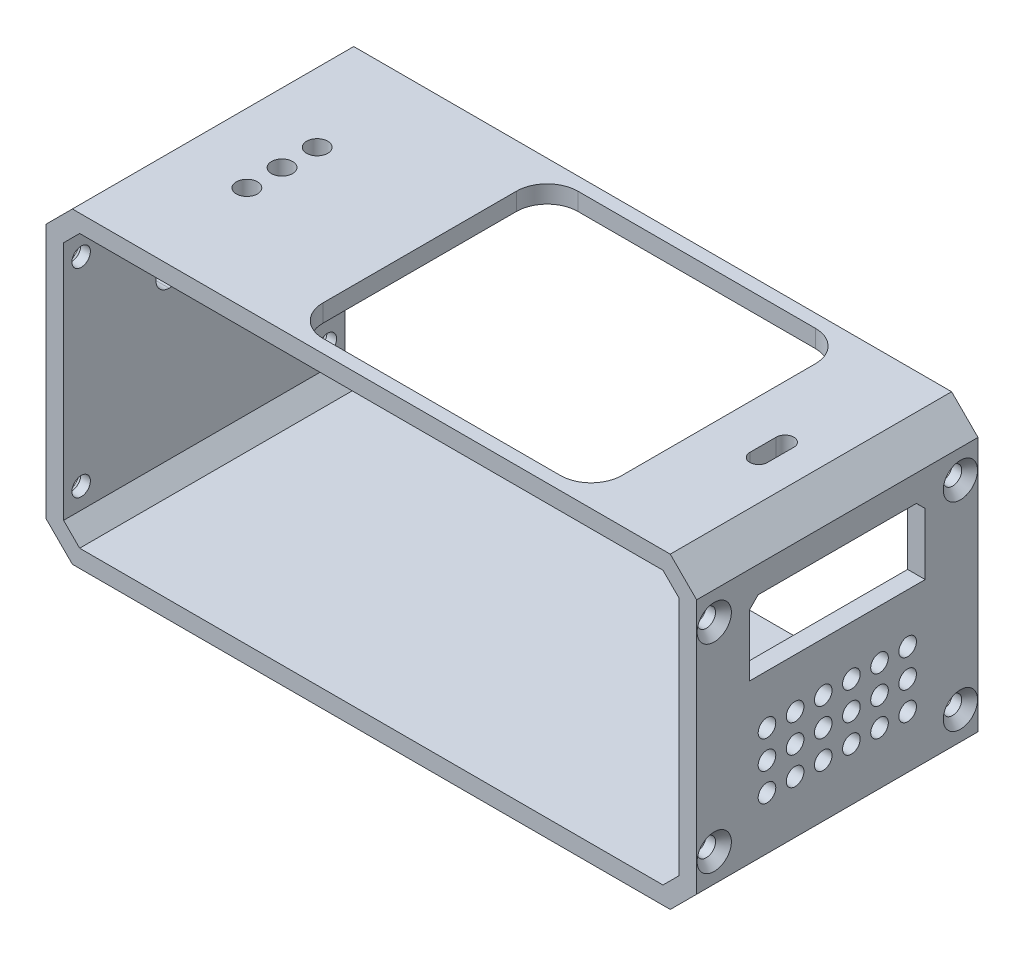
SolidWorks part; units mm, degrees
ref_plane "前视基准面" through (0, 0, 0) normal (0, 0, 1) x (1, 0, 0)
ref_plane "上视基准面" through (0, 0, 0) normal (0, 1, 0) x (1, 0, 0)
ref_plane "右视基准面" through (0, 0, 0) normal (1, 0, 0) x (0, 0, -1)
other "Configuration Table"
sketch "草图1" plane through (0, 0, 0) normal (0, 1, 0) x (1, 0, 0)
  line L0 (-32.2834, 0.435) -> (-71.9856, 0.435) construction
  line L1 (-36.9634, 16.435) -> (37.0366, 16.435)
  line L2 (-36.9634, 16.435) -> (-36.9634, -15.565)
  line L3 (-36.9634, -15.565) -> (37.0366, -15.565)
  line L4 (37.0366, 16.435) -> (37.0366, -15.565)
  line L6 (-32.2834, 11.935) -> (-32.2834, -11.065) construction
  point P6 (-36.9634, 0.435)
  point P9 (-32.2834, 0.435)
  dimension "D1" = 32
  dimension "D2" = 74
extrude "凸台-拉伸1" add sketch "草图1" along normal blind 35
chamfer "倒角1" distance 3 angle 45 4 edges at (37.0366, 0, -0.435) (-36.9634, 0, -0.435) (-36.9634, 35, -0.435) (37.0366, 35, -0.435)
sketch "草图2" plane through (0, 0, 15.565) normal (0, 0, 1) x (1, 0, 0)
  line L8 (-33.135, 2) -> (33.2082, 2)
  line L9 (35.0366, 3.8284) -> (35.0366, 31.1716)
  line L10 (33.2082, 33) -> (-33.135, 33)
  line L11 (-34.9634, 31.1716) -> (-34.9634, 3.8284)
  line L12 (-33.135, 2) -> (33.2082, 2)
  line L13 (35.0366, 3.8284) -> (35.0366, 31.1716)
  line L14 (33.2082, 33) -> (-33.135, 33)
  line L15 (-34.9634, 31.1716) -> (-34.9634, 3.8284)
  line L16 (33.2082, 2) -> (35.0366, 3.8284)
  line L17 (33.2082, 2) -> (35.0366, 3.8284)
  line L18 (35.0366, 31.1716) -> (33.2082, 33)
  line L19 (35.0366, 31.1716) -> (33.2082, 33)
  line L20 (-33.135, 33) -> (-34.9634, 31.1716)
  line L21 (-33.135, 33) -> (-34.9634, 31.1716)
  line L22 (-34.9634, 3.8284) -> (-33.135, 2)
  line L23 (-34.9634, 3.8284) -> (-33.135, 2)
  dimension "D1" = 2
extrude "切除-拉伸1" cut sketch "草图2" against normal through all
sketch "草图4" plane through (0, 35, 0) normal (0, 1, 0) x (1, 0, 0)
  line L0 (34.0366, 16.435) -> (-33.9634, 16.435) construction
  line L1 (-6.9634, 14.935) -> (20.0366, 14.935)
  line L2 (-10.4634, 11.435) -> (-10.4634, -10.565)
  line L3 (-6.9634, -14.065) -> (20.0366, -14.065)
  line L4 (23.5366, 11.435) -> (23.5366, -10.565)
  line L5 (-33.9634, -15.565) -> (34.0366, -15.565) construction
  line L7 (37.0366, 16.435) -> (37.0366, -15.565) construction
  arc A0 (20.0366, -14.065) -> (23.5366, -10.565) centre (20.0366, -10.565) ccw
  arc A1 (20.0366, 14.935) -> (23.5366, 11.435) centre (20.0366, 11.435) cw
  arc A2 (-10.4634, -10.565) -> (-6.9634, -14.065) centre (-6.9634, -10.565) ccw
  arc A3 (-6.9634, 14.935) -> (-10.4634, 11.435) centre (-6.9634, 11.435) ccw
  point P14 (23.5366, -14.065)
  point P17 (23.5366, 14.935)
  point P22 (-10.4634, 14.935)
  dimension "D5" = 3.5
  dimension "D1" = 34
  dimension "D2" = 1.5
  dimension "D3" = 1.5
  dimension "D4" = 13.5
extrude "切除-拉伸2" cut sketch "草图4" against normal up to next
sketch "草图5" plane through (0, 35, 0) normal (0, 1, 0) x (1, 0, 0)
  line L0 (-36.9634, 0.435) -> (-43.9993, 0.435) construction
  circle A0 centre (-26.1174, 0.435) radius 1.2
  circle A1 centre (-26.1174, 4.435) radius 1.2
  circle A2 centre (-26.1174, -3.565) radius 1.2
  dimension "D3" = 2.4
  dimension "D1" = 4
  dimension "D2" = 4
extrude "切除-拉伸3" cut sketch "草图5" against normal up to next
sketch "草图6" plane through (37.0366, 0, 0) normal (1, 0, 0) x (0, 0, -1)
  circle A0 centre (-13.565, 28.8) radius 1.05
  circle A1 centre (-13.565, 6.2) radius 1.05
  circle A2 centre (14.435, 6.2) radius 1.05
  circle A3 centre (14.435, 28.8) radius 1.05
  dimension "D1" = 2.1
extrude "切除-拉伸4" cut sketch "草图6" against normal through all
chamfer "倒角2" distance 0.9 angle 45 8 edges at (37.0366, 28.8, -15.485) (37.0366, 6.2, -15.485) (37.0366, 28.8, 12.515) (37.0366, 6.2, 12.515) (-36.9634, 6.2, -15.485) (-36.9634, 28.8, -15.485) (-36.9634, 6.2, 12.515) (-36.9634, 28.8, 12.515)
sketch "草图7" plane through (0, 35, 0) normal (0, 1, 0) x (1, 0, 0)
  line L0 (34.0366, 0.435) -> (47.8552, 0.435) construction
  line L2 (29.5366, 1.9891) -> (29.5366, -1.0109) construction
  line L3 (30.5366, 1.9891) -> (30.5366, -1.0109)
  line L4 (28.5366, 1.9891) -> (28.5366, -1.0109)
  line L5 (37.0366, 16.435) -> (37.0366, -15.565) construction
  arc A0 (30.5366, 1.9891) -> (28.5366, 1.9891) centre (29.5366, 1.9891) ccw
  arc A1 (28.5366, -1.0109) -> (30.5366, -1.0109) centre (29.5366, -1.0109) ccw
  point P3 (29.5366, 0.4891)
  dimension "D3" = 1
  dimension "D1" = 7.5
  dimension "D2" = 3
extrude "切除-拉伸5" cut sketch "草图7" against normal up to next
sketch "草图8" plane through (-36.9634, 0, 0) normal (-1, 0, 0) x (0, 0, 1)
  line L0 (-2.435, 11.4156) -> (-2.435, -8.1835) construction
  line L1 (-8.435, 22.2) -> (3.565, 22.2) construction
  line L2 (-8.435, 23.7) -> (3.565, 23.7)
  line L3 (-8.435, 20.7) -> (3.565, 20.7)
  line L4 (-16.435, 32) -> (-16.435, 3) construction
  line L5 (-16.435, 35) -> (15.565, 35) construction
  arc A0 (-8.435, 23.7) -> (-8.435, 20.7) centre (-8.435, 22.2) ccw
  arc A1 (3.565, 20.7) -> (3.565, 23.7) centre (3.565, 22.2) ccw
  point P3 (-2.435, 22.2)
  dimension "D4" = 1.5
  dimension "D1" = 14
  dimension "D2" = 12
  dimension "D3" = 12.8
extrude "切除-拉伸6" cut sketch "草图8" against normal up to next
sketch "草图9" plane through (-36.9634, 0, 0) normal (-1, 0, 0) x (0, 0, 1)
  line L0 (-16.435, 32) -> (-16.435, 3) construction
  line L1 (-7.435, 17) -> (-3.435, 17)
  line L2 (-7.435, 17) -> (-7.435, 15)
  line L3 (-7.435, 15) -> (-3.435, 15)
  line L4 (-3.435, 17) -> (-3.435, 15)
  line L5 (-16.435, 35) -> (15.565, 35) construction
  dimension "D1" = 9
  dimension "D2" = 2
  dimension "D3" = 18
  dimension "D4" = 4
extrude "切除-拉伸7" cut sketch "草图9" against normal up to next
fillet "圆角1" radius 1 4 edges at (-35.9634, 15, -3.435) (-35.9634, 17, -3.435) (-35.9634, 17, -7.435) (-35.9634, 15, -7.435)
sketch "草图10" plane through (-36.9634, 0, 0) normal (-1, 0, 0) x (0, 0, 1)
  line L0 (-16.435, 35) -> (15.565, 35) construction
  line L1 (-16.435, 32) -> (-16.435, 3) construction
  circle A0 centre (-8.935, 28.6) radius 1
  circle A1 centre (-5.735, 28.6) radius 1
  circle A2 centre (-2.535, 28.6) radius 1
  circle A3 centre (0.665, 28.6) radius 1
  circle A4 centre (3.865, 28.6) radius 1
  circle A5 centre (-5.735, 25.4) radius 1
  circle A6 centre (-2.535, 25.4) radius 1
  circle A7 centre (0.665, 25.4) radius 1
  circle A8 centre (3.865, 25.4) radius 1
  circle A9 centre (-8.935, 25.4) radius 1
  dimension "D3" = 2
  dimension "D1" = 6.4
  dimension "D2" = 7.5
  dimension "D4" = 5
  dimension "D5" = 2
extrude "切除-拉伸8" cut sketch "草图10" against normal up to next
sketch "草图11" plane through (37.0366, 0, 0) normal (1, 0, 0) x (0, 0, -1)
  line L0 (-15.565, 3) -> (16.435, 3) construction
  line L1 (-8.565, 29) -> (9.435, 29)
  line L3 (-9.565, 21) -> (10.4292, 21)
  line L5 (-15.565, 35) -> (16.435, 35) construction
  line L7 (-9.565, 28) -> (-8.565, 29)
  line L9 (-9.565, 28) -> (-9.565, 21)
  line L14 (10.4292, 28) -> (10.4292, 21)
  line L17 (-9.565, 22.5) -> (-9.565, 16.5) construction
  line L18 (9.435, 29) -> (10.4292, 28)
  point P6 (0.435, 3)
  point P7 (0.435, 29)
  dimension "D1" = 18
  dimension "D2" = 7
  dimension "D3" = 6
  dimension "D4" = 8
extrude "切除-拉伸9" cut sketch "草图11" against normal up to next
sketch "草图12" plane through (37.0366, 0, 0) normal (1, 0, 0) x (0, 0, -1)
  line L0 (16.435, 0) -> (-15.565, 0) construction
  line L1 (-15.565, 0) -> (-15.565, 3) construction
  line L2 (-8.565, 28) -> (-8.565, 12.1375) construction
  circle A0 centre (-7.565, 9) radius 1
  circle A1 centre (-4.365, 9) radius 1
  circle A2 centre (-1.165, 9) radius 1
  circle A3 centre (2.035, 9) radius 1
  circle A4 centre (5.235, 9) radius 1
  circle A5 centre (8.435, 9) radius 1
  circle A6 centre (-4.365, 12.2) radius 1
  circle A7 centre (-1.165, 12.2) radius 1
  circle A8 centre (2.035, 12.2) radius 1
  circle A9 centre (5.235, 12.2) radius 1
  circle A10 centre (8.435, 12.2) radius 1
  circle A11 centre (-4.365, 15.4) radius 1
  circle A12 centre (-1.165, 15.4) radius 1
  circle A13 centre (2.035, 15.4) radius 1
  circle A14 centre (5.235, 15.4) radius 1
  circle A15 centre (8.435, 15.4) radius 1
  circle A16 centre (-7.565, 12.2) radius 1
  circle A17 centre (-7.565, 15.4) radius 1
  dimension "D1" = 2
  dimension "D2" = 9
  dimension "D3" = 8
extrude "切除-拉伸10" cut sketch "草图12" against normal up to next
